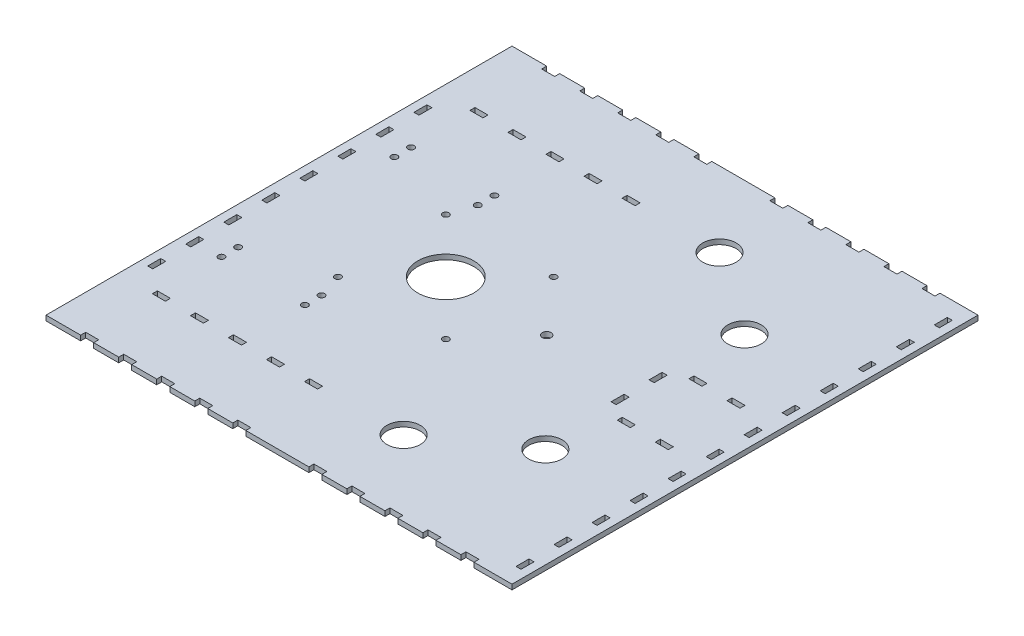
SolidWorks part; units mm, degrees
material "ENPH 253 Hardboard"
ref_plane "Front Plane" through (0, 0, 0) normal (0, 0, 1) x (1, 0, 0)
ref_plane "Top Plane" through (0, 0, 0) normal (0, 1, 0) x (1, 0, 0)
ref_plane "Right Plane" through (0, 0, 0) normal (1, 0, 0) x (0, 0, -1)
sketch "Sketch1" plane through (0, 0, 0) normal (0, 1, 0) x (1, 0, 0)
  line L0 (0, -139.7) -> (0, 139.7) construction
  line L1 (-139.7, 139.7) -> (139.7, 139.7)
  line L2 (-139.7, 139.7) -> (-139.7, -139.7)
  line L3 (-139.7, -139.7) -> (139.7, -139.7)
  line L4 (139.7, 139.7) -> (139.7, -139.7)
  line L5 (-139.7, 139.7) -> (139.7, -139.7) construction
  line L6 (-139.7, -139.7) -> (139.7, 139.7) construction
  line L12 (-139.7, 0) -> (139.7, 0) construction
  point P0 (0, 0)
  dimension "D1" = 279.4
  dimension "D2" = 279.4
extrude "Boss-Extrude1" add sketch "Sketch1" along normal blind 3
sketch "Sketch3" plane through (0, 0, 0) normal (0, -1, 0) x (-1, 0, 0)
  line L0 (-139.7, -139.7) -> (-139.7, 139.7) construction
  line L1 (-134.7, 129.3) -> (-131.7, 129.3)
  line L2 (-134.7, 129.3) -> (-134.7, 121.5)
  line L3 (-134.7, 121.5) -> (-131.7, 121.5)
  line L4 (-131.7, 129.3) -> (-131.7, 121.5)
  line L5 (-139.7, 139.7) -> (139.7, 139.7) construction
  dimension "D1" = 5
  dimension "D2" = 10.4
  dimension "D3" = 7.8
  dimension "D4" = 3
extrude "Cut-Extrude2" cut sketch "Sketch3" against normal through all
pattern_linear "LPattern1" count 12 spacing 22.8 along (0, 0, 1) of "Cut-Extrude2"
sketch "Sketch5" plane through (0, 0, 0) normal (0, -1, 0) x (1, 0, 0)
  line L0 (139.7, -139.7) -> (-139.7, -139.7) construction
  line L1 (109.1, -139.7) -> (116.9, -139.7)
  line L2 (109.1, -139.7) -> (109.1, -136.7)
  line L3 (109.1, -136.7) -> (116.9, -136.7)
  line L4 (116.9, -139.7) -> (116.9, -136.7)
  line L5 (139.7, 139.7) -> (139.7, -139.7) construction
  dimension "D1" = 22.8
  dimension "D2" = 7.8
  dimension "D3" = 3
extrude "Cut-Extrude3" cut sketch "Sketch5" against normal through all
pattern_linear "LPattern2" count 11 spacing 22.8 along (-1, 0, 0) skipping (5, 0) of "Cut-Extrude3"
mirror "Mirror2" about plane through (0, 0, 0) normal (0, 0, 1) of "LPattern2"
sketch "Sketch6" plane through (0, 0, 0) normal (0, -1, 0) x (1, 0, 0)
  line L0 (63.5, -139.7) -> (48.5, -139.7) construction
  line L1 (-134.7, -83.7) -> (-131.7, -83.7)
  line L2 (-134.7, -83.7) -> (-134.7, -75.9)
  line L3 (-134.7, -75.9) -> (-131.7, -75.9)
  line L4 (-131.7, -83.7) -> (-131.7, -75.9)
  line L5 (-139.7, -139.7) -> (-139.7, 139.7) construction
  dimension "D1" = 56
  dimension "D2" = 5
  dimension "D3" = 3
  dimension "D4" = 7.8
extrude "Cut-Extrude4" cut sketch "Sketch6" against normal through all
pattern_linear "LPattern3" count 8 spacing 22.8 along (0, 0, 1) of "Cut-Extrude4"
sketch "Sketch7" plane through (0, 0, 0) normal (0, -1, 0) x (-1, 0, 0)
  line L1 (139.7, 139.7) -> (139.7, -139.7) construction
  line L3 (-63.5, 139.7) -> (-48.5, 139.7) construction
  circle A0 centre (39.7, 0) radius 16.75
  dimension "D1" = 33.5
  dimension "D2" = 100
  dimension "D3" = 139.7
extrude "Cut-Extrude5" cut sketch "Sketch7" against normal through all
hole_wizard "#6 Clearance Hole1" positions "Sketch8" profile "Sketch9" hole size "#6" standard "ANSI Inch" end condition through all
sketch "Sketch8" plane through (0, 3, 0) normal (0, 1, 0) x (1, 0, 0)
  line L0 (-72.025, -32.325) -> (-72.025, 32.325) construction
  line L1 (-72.025, 32.325) -> (-7.375, 32.325) construction
  line L2 (-7.375, 32.325) -> (-7.375, -32.325) construction
  line L3 (-7.375, -32.325) -> (-72.025, -32.325) construction
  point P0 (-72.025, -32.325)
  point P2 (-72.025, 32.325)
  point P4 (-7.375, 32.325)
  point P6 (-7.375, -32.325)
  dimension "D1" = 64.65
  dimension "D2" = 64.65
  dimension "D3" = 90
  dimension "D4" = 64.65
  dimension "D5" = 32.325
  dimension "D6" = 32.325
sketch "Sketch9" plane through (-72.025, 3, 32.325) normal (1, 0, 0) x (0, 0, 1)
  line L0 (0, 0) -> (0, 3)
  line L1 (0, 3) -> (1.8986, 3)
  line L2 (1.8986, 3) -> (1.8986, 0)
  line L5 (1.8986, 0) -> (0, 0)
  line L11 (0, -6.35) -> (0, 107.95) construction
  dimension "Thru Hole Dia." = 3.7973
  dimension "Thru Hole Depth" = 3
hole_wizard "#6 Clearance Hole2" positions "Sketch10" profile "Sketch11" hole size "#6" standard "ANSI Inch" end condition through all
sketch "Sketch10" plane through (0, 3, 0) normal (0, 1, 0) x (1, 0, 0)
  line L1 (-118.9, 139.7) -> (-139.7, 139.7) construction
  line L2 (-139.7, -139.7) -> (-118.9, -139.7) construction
  line L3 (-73.3, 139.7) -> (-88.3, 139.7) construction
  line L4 (-88.3, -139.7) -> (-73.3, -139.7) construction
  line L5 (-139.7, 139.7) -> (-139.7, -139.7) construction
  point P0 (-117.36, 56.83)
  point P2 (-67.36, 56.83)
  point P4 (-117.36, -56.83)
  point P6 (-67.36, -56.83)
  point P22 (-67.36, -46.83)
  point P24 (-117.36, -46.83)
  point P26 (-67.36, 46.83)
  point P28 (-117.36, 46.83)
  dimension "D2" = 50
  dimension "D3" = 22.34
  dimension "D4" = 50
  dimension "D5" = 82.87
  dimension "D6" = 82.87
  dimension "D7" = 82.87
  dimension "D8" = 82.87
  dimension "D9" = 10
  dimension "D10" = 10
  dimension "D11" = 50
  dimension "D12" = 10
  dimension "D13" = 10
  dimension "D14" = 50
  dimension "D15" = 22.34
  dimension "D16" = 22.34
  dimension "D17" = 22.34
sketch "Sketch11" plane through (-117.36, 3, -56.83) normal (1, 0, 0) x (0, 0, 1)
  line L0 (0, 0) -> (0, 3)
  line L1 (0, 3) -> (1.8986, 3)
  line L2 (1.8986, 3) -> (1.8986, 0)
  line L5 (1.8986, 0) -> (0, 0)
  line L11 (0, -6.35) -> (0, 107.95) construction
  dimension "Thru Hole Dia." = 3.7973
  dimension "Thru Hole Depth" = 3
sketch "Sketch14" plane through (0, 0, 0) normal (0, -1, 0) x (-1, 0, 0)
  line L0 (139.7, 139.7) -> (139.7, -139.7) construction
  line L1 (-17.9, 139.7) -> (19.9, 139.7) construction
  circle A0 centre (-20.8, 0) radius 2.65
  dimension "D1" = 5.3
  dimension "D2" = 160.5
  dimension "D3" = 139.7
extrude "Cut-Extrude6" cut sketch "Sketch14" against normal through all
sketch "Sketch16" plane through (0, 0, 0) normal (0, -1, 0) x (1, 0, 0)
  line L0 (-139.7, -139.7) -> (-139.7, 139.7) construction
  line L1 (-118.9, 96.7) -> (-111.1, 96.7)
  line L2 (-118.9, 96.7) -> (-118.9, 93.7)
  line L3 (-118.9, 93.7) -> (-111.1, 93.7)
  line L4 (-111.1, 96.7) -> (-111.1, 93.7)
  line L7 (-111.1, 136.7) -> (-118.9, 136.7) construction
  dimension "D1" = 20.8
  dimension "D2" = 7.8
  dimension "D3" = 40
  dimension "D4" = 3
extrude "Cut-Extrude8" cut sketch "Sketch16" against normal through all
pattern_linear "LPattern5" count 5 spacing 22.8 along (1, 0, 0) of "Cut-Extrude8"
mirror "Mirror4" about plane through (0, 0, 0) normal (0, 0, 1) of "LPattern5"
sketch "Sketch17" plane through (0, 0, 0) normal (0, -1, 0) x (1, 0, 0)
  line L1 (116.7, 23) -> (108.9, 23)
  line L2 (116.7, 23) -> (116.7, 20)
  line L3 (116.7, 20) -> (108.9, 20)
  line L4 (108.9, 23) -> (108.9, 20)
  line L5 (94.1, 139.7) -> (109.1, 139.7) construction
  line L6 (139.7, 139.7) -> (139.7, -139.7) construction
  point P8 (116.7, 21.5)
  dimension "D1" = 116.7
  dimension "D2" = 23
  dimension "D3" = 7.8
  dimension "D4" = 3
extrude "Cut-Extrude9" cut sketch "Sketch17" against normal through all
pattern_linear "LPattern6" count 2 spacing 22.8 along (-1, 0, 0) of "Cut-Extrude9"
sketch "Sketch18" plane through (0, 0, 0) normal (0, -1, 0) x (-1, 0, 0)
  line L0 (-139.7, -139.7) -> (-139.7, 139.7) construction
  line L1 (-77.7, -15.3) -> (-74.7, -15.3)
  line L2 (-77.7, -15.3) -> (-77.7, -7.5)
  line L3 (-77.7, -7.5) -> (-74.7, -7.5)
  line L4 (-74.7, -15.3) -> (-74.7, -7.5)
  line L5 (-71.3, -139.7) -> (-86.3, -139.7) construction
  dimension "D1" = 7.8
  dimension "D2" = 3
  dimension "D3" = 62
  dimension "D4" = 124.4
extrude "Cut-Extrude10" cut sketch "Sketch18" against normal through all
mirror "Mirror5" about plane through (0, 0, 0) normal (0, 0, 1) of "Cut-Extrude10", "LPattern6", "Cut-Extrude9"
sketch "Sketch19" plane through (0, 0, 0) normal (0, -1, 0) x (1, 0, 0)
  line L0 (-19.9, 139.7) -> (17.9, 139.7) construction
  line L1 (17.9, -139.7) -> (-19.9, -139.7) construction
  line L2 (139.7, 139.7) -> (139.7, -139.7) construction
  line L3 (116.9, 139.7) -> (139.7, 139.7) construction
  line L4 (86.3, -139.7) -> (71.3, -139.7) construction
  circle A0 centre (29.7, 94.7) radius 10
  circle A1 centre (79.7, 59.7) radius 10
  circle A2 centre (29.7, -94.7) radius 10
  circle A3 centre (79.7, -59.7) radius 10
  dimension "D9" = 20
  dimension "D10" = 20
  dimension "D11" = 20
  dimension "D12" = 20
  dimension "D1" = 45
  dimension "D2" = 45
  dimension "D3" = 110
  dimension "D4" = 110
  dimension "D5" = 60
  dimension "D6" = 80
  dimension "D7" = 60
  dimension "D8" = 80
extrude "Cut-Extrude11" cut sketch "Sketch19" against normal through all
